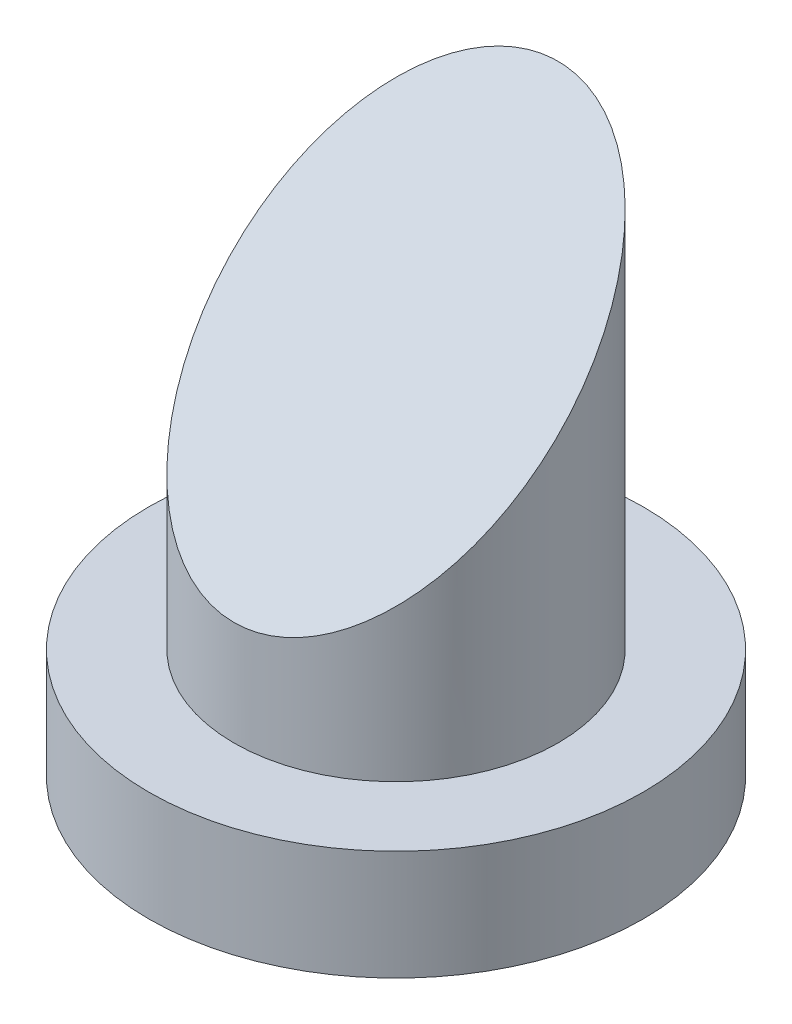
SolidWorks part; units mm, degrees
material "PTFE (general)"
ref_plane "Front Plane" through (0, 0, 0) normal (0, 0, 1) x (1, 0, 0)
ref_plane "Top Plane" through (0, 0, 0) normal (0, 1, 0) x (1, 0, 0)
ref_plane "Right Plane" through (0, 0, 0) normal (1, 0, 0) x (0, 0, -1)
sketch "Sketch1" plane through (0, 0, 0) normal (0, 1, 0) x (1, 0, 0)
  circle A0 centre (0, 0) radius 9
  dimension "D1" = 18
extrude "Boss-Extrude1" add sketch "Sketch1" along normal blind 4
sketch "Sketch2" plane through (0, 4, 0) normal (0, 1, 0) x (1, 0, 0)
  circle A0 centre (0, 0) radius 5.9
  dimension "D1" = 11.8
extrude "Boss-Extrude2" add sketch "Sketch2" along normal blind 20
sketch "Sketch3" plane through (0, 0, 0) normal (1, 0, 0) x (0, 0, -1)
  line L0 (-6.28, 7.42) -> (6.28, 19.98)
  line L2 (9, 4) -> (-9, 4) construction
  line L4 (-6.28, 7.42) -> (-6.28, 28.7719)
  line L5 (-6.28, 28.7719) -> (6.28, 28.7719)
  line L6 (6.28, 19.98) -> (6.28, 28.7719)
  point P2 (0, 13.7)
  dimension "D1" = 12.56
  dimension "D2" = 45
  dimension "D3" = 12.56
  dimension "D4" = 6.28
  dimension "D5" = 9.7
extrude "Cut-Extrude1" cut sketch "Sketch3" against normal through all both and the other way through all contours L0 L6 L5 L4 region at (0, 20.7998, 0.8722)
